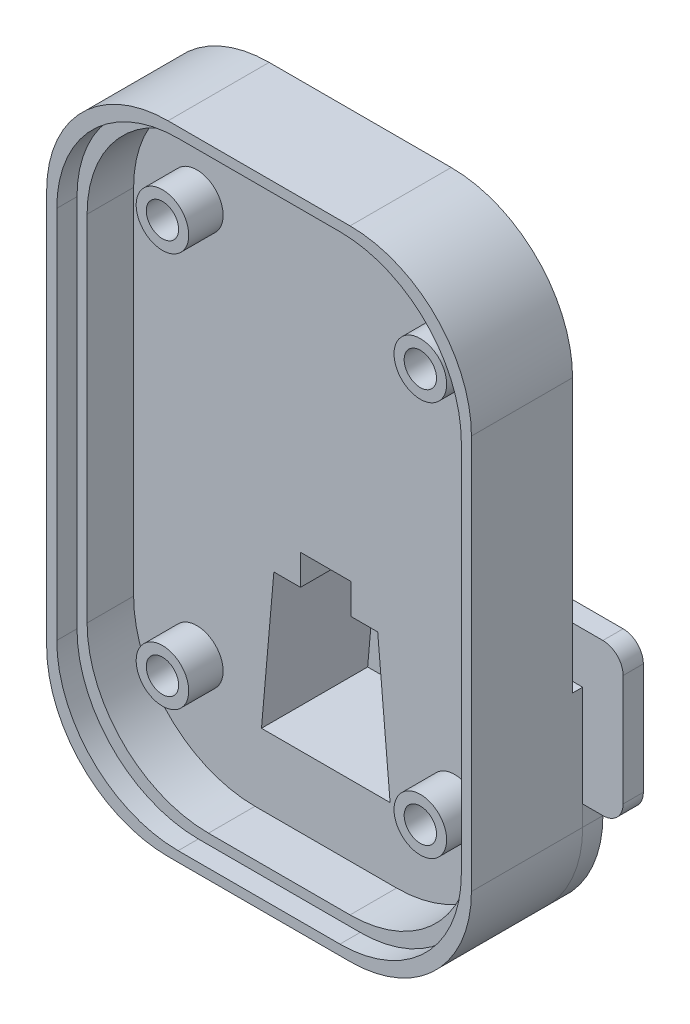
SolidWorks part; units mm, degrees
ref_plane "前视基准面" through (0, 0, 0) normal (0, 0, 1) x (1, 0, 0)
ref_plane "上视基准面" through (0, 0, 0) normal (0, 1, 0) x (1, 0, 0)
ref_plane "右视基准面" through (0, 0, 0) normal (1, 0, 0) x (0, 0, -1)
sketch "草图2" plane through (0, 0, 0) normal (0, 0, 1) x (1, 0, 0)
  line L1 (-21, 31.5) -> (21, 31.5)
  line L2 (-21, 31.5) -> (-21, -31.5)
  line L3 (-21, -31.5) -> (21, -31.5)
  line L4 (21, 31.5) -> (21, -31.5)
  line L5 (-21, 31.5) -> (21, -31.5) construction
  line L6 (-21, -31.5) -> (21, 31.5) construction
  point P0 (0, 0)
extrude "凸台-拉伸1" add sketch "草图2" along normal blind 10
sketch "草图3" plane through (0, 0, 0) normal (0, 0, -1) x (-1, 0, 0)
  line L0 (21, 31.5) -> (21, -31.5) construction
  line L1 (-21, -31.5) -> (21, -31.5)
  line L2 (-21, -31.5) -> (-21, -7.5)
  line L3 (-21, -7.5) -> (21, -7.5)
  line L4 (21, -31.5) -> (21, -7.5)
extrude "凸台-拉伸2" add sketch "草图3" along normal blind 8
sketch "草图4" plane through (0, -7.5, 0) normal (0, 1, 0) x (1, 0, 0)
  line L3 (4.8333, 2) -> (3.5, 0)
  line L4 (21, 0) -> (-21, 0) construction
  line L6 (-3.5, 0) -> (3.5, 0)
  line L8 (0, 8) -> (0, 0) construction
  line L9 (-21, 8) -> (21, 8) construction
  line L10 (4.8333, 2) -> (-4.8333, 2)
  line L11 (-4.8333, 2) -> (-3.5, 0)
  point P12 (0, 2)
  dimension "D1" = 2
  dimension "D2" = 123.69
  dimension "D3" = 3.5
extrude "凸台-拉伸3" add sketch "草图4" along normal blind 32
sketch "草图5" plane through (0, -7.5, 0) normal (0, 1, 0) x (1, 0, 0)
  line L0 (0, 5.25) -> (0, 0)
  line L1 (-3.81, 5.25) -> (3.81, 5.25)
  line L2 (4.8333, 2) -> (-4.8333, 2) construction
  line L3 (-5.05, 4) -> (5.05, 4)
  line L4 (-5.05, 4) -> (-5.05, 6.5)
  line L5 (-5.05, 6.5) -> (5.05, 6.5)
  line L6 (5.05, 4) -> (5.05, 6.5)
  line L7 (-5.05, 4) -> (5.05, 6.5) construction
  line L8 (-5.05, 6.5) -> (5.05, 4) construction
  line L9 (3.5, 0) -> (21, 0) construction
  circle A0 centre (1.27, 5.25) radius 0.74
  circle A1 centre (3.81, 5.25) radius 0.74
  circle A2 centre (-1.27, 5.25) radius 0.74
  circle A3 centre (-3.81, 5.25) radius 0.74
  point P2 (0, 5.25)
  point P5 (0, 5.25)
  dimension "D3" = 2.5
  dimension "D4" = 1.48
  dimension "D1" = 5.25
  dimension "D2" = 10.1
  dimension "D5" = 2
  dimension "D6" = 3
extrude "切除-拉伸1" cut sketch "草图5" against normal blind 10 contours A3 | A2 | A0 | A1
sketch "草图6" plane through (0, 0, -8) normal (0, 0, -1) x (-1, 0, 0)
  line L0 (-9.55, -7.5) -> (-21, -7.5)
  line L2 (0, 0) -> (0, -31.5) construction
  line L3 (-11, -29.5) -> (11, -29.5)
  line L4 (19, -17.5) -> (19, -21.5)
  line L5 (-9.55, -23.5) -> (9.55, -23.5)
  line L6 (21, -17.5) -> (19, -17.5)
  line L7 (9.55, -7.5) -> (9.55, -19.5)
  line L8 (9.55, -7.5) -> (21, -7.5)
  line L9 (21, -7.5) -> (21, -17.5)
  line L10 (-9.55, -23.5) -> (-13.55, -23.5) construction
  line L11 (-21, -31.5) -> (21, -31.5) construction
  line L13 (-21, -7.5) -> (-21, -17.5)
  line L15 (-9.55, -7.5) -> (-9.55, -19.5)
  line L16 (-21, -17.5) -> (-19, -17.5)
  line L17 (-21, -17.5) -> (-21, -31.5)
  line L19 (-19, -17.5) -> (-19, -21.5)
  line L20 (-21, -17.5) -> (-21, -7.5)
  line L40 (-21, -7.5) -> (-21, -17.5)
  arc A0 (-11, -29.5) -> (-19, -21.5) centre (-11, -21.5) cw
  arc A1 (-9.55, -19.5) -> (-13.55, -23.5) centre (-9.55, -23.5) ccw
  arc A2 (-13.55, -23.5) -> (-9.55, -23.5) centre (-11.55, -23.5) ccw
  arc A3 (9.55, -19.5) -> (13.55, -23.5) centre (9.55, -23.5) cw
  arc A4 (13.55, -23.5) -> (9.55, -23.5) centre (11.55, -23.5) cw
  arc A5 (11, -29.5) -> (19, -21.5) centre (11, -21.5) ccw
  dimension "D7" = 8
  dimension "D10" = 2
  dimension "D11" = 4
  dimension "D2" = 11.45
  dimension "D3" = 10
  dimension "D4" = 6
  dimension "D5" = 2
  dimension "D6" = 2
  dimension "D15" = 12
extrude "切除-拉伸2" cut sketch "草图6" against normal blind 7
sketch "草图8" plane through (0, 0, -1) normal (0, 0, -1) x (-1, 0, 0)
  line L0 (0, -26.5) -> (6, -26.5)
  line L1 (-21, -17.5) -> (-21, -31.5) construction
  line L2 (-9.55, -23.5) -> (9.55, -23.5) construction
  line L4 (0, -26.5) -> (-6, -26.5)
  circle A0 centre (-6, -26.5) radius 1.6
  circle A1 centre (6, -26.5) radius 1.6
  point P2 (0, 0)
  point P4 (0, 0)
  dimension "D2" = 3
  dimension "D3" = 3.2
  dimension "D1" = 6
  dimension "D4" = 21
extrude "切除-拉伸4" cut sketch "草图8" against normal blind 3
fillet "圆角6" radius 12 4 edges at (21, -31.5, 1) (-21, -31.5, 1) (-21, 31.5, 5) (21, 31.5, 5)
sketch "草图43" plane through (0, 0, -8) normal (0, 0, -1) x (-1, 0, 0)
  line L0 (-9.55, -7.5) -> (-7.55, -7.5)
  line L1 (9.55, -7.5) -> (-9.55, -7.5) construction
  line L2 (21, -17.5) -> (21, -7.5) construction
  line L3 (-7.55, -7.5) -> (-21, -7.5)
  line L4 (-7.55, -23.5) -> (-7.55, -31.5)
  line L5 (-7.55, -31.5) -> (-21, -31.5)
  line L6 (-21, -7.5) -> (-21, -31.5)
  line L7 (-9.55, -7.5) -> (-9.55, -19.5) construction
  line L8 (0, 9.9) -> (0, -9.9) construction
  line L13 (9.55, -7.5) -> (7.55, -7.5)
  line L14 (-7.55, -7.5) -> (-6.55, -7.5)
  line L15 (-3.5, -7.5) -> (-21, -7.5) construction
  line L16 (-6.55, -7.5) -> (-7.55, -23.5)
  line L17 (-9.55, -23.5) -> (9.55, -23.5) construction
  line L18 (21, -7.5) -> (21, -31.5)
  line L19 (7.55, -31.5) -> (21, -31.5)
  line L20 (7.55, -23.5) -> (7.55, -31.5)
  line L21 (6.55, -7.5) -> (7.55, -23.5)
  line L22 (7.55, -7.5) -> (6.55, -7.5)
  line L23 (7.55, -7.5) -> (21, -7.5)
  line L24 (9.55, -7.5) -> (7.55, -7.5)
  dimension "D1" = 24
  dimension "D2" = 42
  dimension "D3" = 2
  dimension "D4" = 1
  dimension "D5" = 2
extrude "切除-拉伸21" cut sketch "草图43" against normal blind 7
sketch "草图10" plane through (0, 0, 0) normal (0, 0, 1) x (1, 0, 0)
  line L1 (10.55, -23.5) -> (16.55, -23.5) construction
  line L2 (23, -2.5) -> (14.55, -2.5)
  line L3 (0, -9.9) -> (0, 9.9) construction
  line L5 (21, -7.5) -> (21, -19.5) construction
  line L7 (17.55, 1.7) -> (17.55, 2.7)
  line L8 (17.55, 2.7) -> (15.2406, 6.7)
  line L9 (15.2406, 6.7) -> (10.55, 6.7)
  line L10 (10.55, 6.7) -> (10.55, -17.5)
  line L20 (17.55, 2.7) -> (17.55, 6.7) construction
  line L35 (25, -4.5) -> (25, -15.5)
  line L43 (17.55, 1.7) -> (14.55, 1.7)
  line L44 (14.55, 1.7) -> (14.55, -2.5)
  line L58 (0, 0) -> (0, -29.5) construction
  line L62 (23, -17.5) -> (21, -17.5)
  line L63 (21, -19.5) -> (21, 19.5) construction
  line L64 (21, -17.5) -> (21, -19.5)
  line L66 (-9, -31.5) -> (9, -31.5) construction
  line L67 (9, -31.5) -> (7.55, -31.5)
  line L68 (10.55, -23.5) -> (-10.55, -23.5)
  line L79 (-7.55, -29.5) -> (7.55, -29.5)
  line L80 (7.55, -29.5) -> (7.55, -31.5)
  line L81 (-17.55, 2.7) -> (-17.55, 6.7) construction
  line L82 (-10.55, -23.5) -> (-16.55, -23.5) construction
  line L83 (-7.55, -29.5) -> (-7.55, -31.5)
  line L84 (-9, -31.5) -> (-7.55, -31.5)
  line L85 (-21, -17.5) -> (-21, -19.5)
  line L86 (-23, -17.5) -> (-21, -17.5)
  line L87 (-14.55, 1.7) -> (-14.55, -2.5)
  line L88 (-17.55, 1.7) -> (-14.55, 1.7)
  line L89 (-25, -4.5) -> (-25, -15.5)
  line L90 (-10.55, 6.7) -> (-10.55, -17.5)
  line L91 (-15.2406, 6.7) -> (-10.55, 6.7)
  line L92 (-17.55, 2.7) -> (-15.2406, 6.7)
  line L93 (-17.55, 1.7) -> (-17.55, 2.7)
  line L94 (-23, -2.5) -> (-14.55, -2.5)
  arc A4 (10.55, -23.5) -> (16.55, -23.5) centre (13.55, -23.5) ccw
  arc A5 (16.55, -23.5) -> (10.55, -17.5) centre (10.55, -23.5) ccw
  circle A6 centre (6, -26.5) radius 1.6
  arc A10 (25, -15.5) -> (23, -17.5) centre (23, -15.5) cw
  arc A11 (23, -2.5) -> (25, -4.5) centre (23, -4.5) cw
  arc A13 (21, -19.5) -> (9, -31.5) centre (9, -19.5) cw
  arc A20 (-21, -19.5) -> (-9, -31.5) centre (-9, -19.5) ccw
  arc A21 (-23, -2.5) -> (-25, -4.5) centre (-23, -4.5) ccw
  arc A22 (-25, -15.5) -> (-23, -17.5) centre (-23, -15.5) ccw
  circle A23 centre (-6, -26.5) radius 1.6
  arc A24 (-16.55, -23.5) -> (-10.55, -17.5) centre (-10.55, -23.5) cw
  arc A25 (-10.55, -23.5) -> (-16.55, -23.5) centre (-13.55, -23.5) cw
  point P37 (0, -23.5)
  point P40 (25, -17.5)
  point P48 (25, -2.5)
  point P52 (0, -29.5)
  point P54 (0, -23.5)
  point P55 (0, -31.5)
  point P56 (0, -23.5)
  point P58 (0, -23.5)
  point P69 (-25, -2.5)
  point P70 (-25, -17.5)
  dimension "D7" = 2
  dimension "D8" = 4
  dimension "D9" = 3
  dimension "D10" = 4.2
  dimension "D11" = 30
  dimension "D12" = 6
  dimension "D13" = 5
  dimension "D3" = 3.2
  dimension "D5" = 3
  dimension "D15" = 2
  dimension "D16" = 2
  dimension "D4" = 15
  dimension "D2" = 10.45
  dimension "D6" = 7
  dimension "D14" = 1
  dimension "D17" = 7.55
  dimension "D18" = 2
extrude "弹性件" add sketch "草图10" along normal blind 2 from offset 3 separate body
sketch "草图14" plane through (0, 0, 10) normal (0, 0, 1) x (1, 0, 0)
  line L0 (21, -19.5) -> (21, 19.5) construction
  line L1 (-7, -29.5) -> (7, -29.5)
  line L2 (-19, -17.5) -> (-19, 17.5)
  line L3 (-7, 29.5) -> (7, 29.5)
  line L4 (19, -17.5) -> (19, 17.5)
  line L5 (-19, -29.5) -> (19, 29.5) construction
  line L6 (-19, 29.5) -> (19, -29.5) construction
  line L7 (9, 31.5) -> (-9, 31.5) construction
  arc A0 (-7, -29.5) -> (-19, -17.5) centre (-7, -17.5) cw
  arc A1 (7, -29.5) -> (19, -17.5) centre (7, -17.5) ccw
  arc A2 (7, 29.5) -> (19, 17.5) centre (7, 17.5) cw
  arc A3 (-19, 17.5) -> (-7, 29.5) centre (-7, 17.5) cw
  point P0 (0, 0)
  dimension "D3" = 12
  dimension "D1" = 2
  dimension "D2" = 2
extrude "切除-拉伸5" cut sketch "草图14" against normal blind 6.6
sketch "草图15" plane through (0, 0, 10) normal (0, 0, 1) x (1, 0, 0)
  line L0 (7, 29.5) -> (-7, 29.5) construction
  line L1 (-8, -30.5) -> (8, -30.5)
  line L2 (-20, -18.5) -> (-20, 18.5)
  line L3 (-8, 30.5) -> (8, 30.5)
  line L4 (20, -18.5) -> (20, 18.5)
  line L5 (-20, -30.5) -> (20, 30.5) construction
  line L6 (-20, 30.5) -> (20, -30.5) construction
  line L7 (19, -17.5) -> (19, 17.5) construction
  line L8 (9, 31.5) -> (-9, 31.5) construction
  arc A0 (-8, -30.5) -> (-20, -18.5) centre (-8, -18.5) cw
  arc A1 (8, -30.5) -> (20, -18.5) centre (8, -18.5) ccw
  arc A2 (8, 30.5) -> (20, 18.5) centre (8, 18.5) cw
  arc A3 (-20, 18.5) -> (-8, 30.5) centre (-8, 18.5) cw
  point P0 (0, 0)
  dimension "D3" = 12
  dimension "D1" = 1
  dimension "D2" = 1
  dimension "D4" = 1
extrude "切除-拉伸6" cut sketch "草图15" against normal blind 2
sketch "草图29" plane through (0, 0, 3.4) normal (0, 0, 1) x (1, 0, 0)
  line L0 (9, 31.5) -> (-9, 31.5) construction
  line L1 (-21, 19.5) -> (-21, -19.5) construction
  circle A0 centre (12.75, 19.5259) radius 2.6
  circle A1 centre (-12.75, 19.5259) radius 2.6
  circle A2 centre (-12.75, -19.5) radius 2.6
  circle A3 centre (12.75, -19.5) radius 2.6
  point P14 (0, 0)
  point P17 (0, 0)
  point P18 (0, 0)
  point P19 (0, 0)
  point P20 (0, 0)
  point P21 (0, 0)
  point P22 (0, 0)
  dimension "D1" = 5.2
  dimension "D3" = 8.25
  dimension "D2" = 11.9741
extrude "凸台-拉伸12" add sketch "草图29" along normal blind 3.4
sketch "草图32" plane through (0, 0, 6.8) normal (0, 0, 1) x (1, 0, 0)
  circle A0 centre (-12.75, 19.5259) radius 1.6
  circle A1 centre (12.75, 19.5259) radius 1.6
  circle A2 centre (12.75, -19.5) radius 1.6
  circle A3 centre (-12.75, -19.5) radius 1.6
extrude "切除-拉伸16" cut sketch "草图32" against normal blind 2.4
sketch "草图36" plane through (0, 0, 3.4) normal (0, 0, 1) x (1, 0, 0)
  line L0 (6.05, -7.5) -> (-6.05, -7.5)
  line L1 (-6.05, -7.5) -> (-7.4498, -23.5)
  line L2 (-7.4498, -23.5) -> (7.4498, -23.5)
  line L3 (7.4498, -23.5) -> (6.05, -7.5)
  line L4 (6.3585, -22.5) -> (5.1337, -8.5)
  line L5 (5.1337, -8.5) -> (-5.1337, -8.5)
  line L6 (-5.1337, -8.5) -> (-6.3585, -22.5)
  line L7 (-6.3585, -22.5) -> (6.3585, -22.5)
  line L8 (0, -8.5) -> (0, -18.7)
  line L9 (6.0261, -18.7) -> (-6.0261, -18.7)
  point P17 (0, 0)
  point P18 (0, 0)
  point P19 (0, 0)
  point P20 (0, 0)
  dimension "D1" = 1
  dimension "D2" = 10.2
extrude "切除-拉伸17" cut sketch "草图36" against normal blind 10.5 contours L4 L5 L6 L7
sketch "草图38" plane through (0, -8.5, 0) normal (0, -1, 0) x (-1, 0, 0)
  line L0 (2.5, -3.4) -> (-2.5, -3.4)
  line L1 (-5.1337, -3.4) -> (5.1337, -3.4) construction
  line L2 (2.5, -3.4) -> (2.5, 1.6)
  line L3 (2.5, 1.6) -> (-2.5, 1.6)
  line L4 (-2.5, 1.6) -> (-2.5, -3.4)
  point P5 (0, -3.4)
extrude "切除-拉伸19" cut sketch "草图38" against normal blind 3
